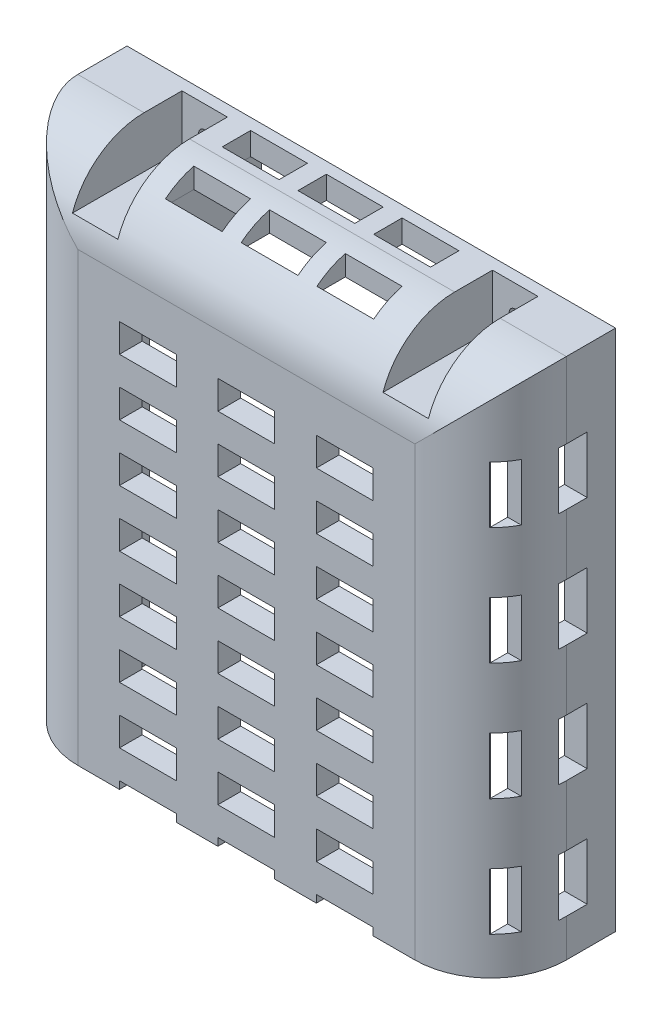
SolidWorks part; units mm, degrees
ref_plane "Plano frontal" through (0, 0, 0) normal (0, 0, 1) x (1, 0, 0)
ref_plane "Plano superior" through (0, 0, 0) normal (0, 1, 0) x (1, 0, 0)
ref_plane "Plano direito" through (0, 0, 0) normal (1, 0, 0) x (0, 0, -1)
sketch "Esboço1" plane through (0, 0, 0) normal (0, 0, 1) x (1, 0, 0)
  line L0 (-47.125, -132) -> (-47.125, -122)
  line L1 (-64.5, 138) -> (64.5, 138)
  line L2 (-64.5, 138) -> (-64.5, -138)
  line L3 (-64.5, -138) -> (64.5, -138)
  line L4 (64.5, 138) -> (64.5, -138)
  line L5 (0, -138) -> (0, 138) construction
  line L6 (-64.5, 0) -> (64.5, 0) construction
  line L7 (-58.5, 132) -> (58.5, 132) construction
  line L8 (-58.5, 132) -> (-58.5, -132) construction
  line L9 (-58.5, -132) -> (58.5, -132) construction
  line L10 (58.5, 132) -> (58.5, -132) construction
  line L11 (0, -132) -> (0, 132) construction
  line L12 (-58.5, 0) -> (58.5, 0) construction
  line L13 (-47.125, -122) -> (-58.5, -122)
  line L14 (-47, 132) -> (-47, 124.5)
  line L15 (-47, 124.5) -> (-35, 124.5)
  line L16 (-35, 124.5) -> (-35, 132)
  line L17 (-41, 130.5) -> (-41, 124.5) construction
  line L18 (-41, 130.5) -> (-35, 130.5) construction
  line L19 (-47, 132) -> (-58.5, 132)
  line L20 (-58.5, 132) -> (-58.5, -122)
  line L21 (41, 130.5) -> (35, 130.5) construction
  line L22 (41, 130.5) -> (41, 124.5) construction
  line L23 (47, 132) -> (58.5, 132)
  line L24 (35, 124.5) -> (35, 132)
  line L25 (47, 124.5) -> (35, 124.5)
  line L26 (47, 132) -> (47, 124.5)
  line L27 (58.5, 132) -> (58.5, -132) construction
  line L28 (58.5, 132) -> (58.5, -122)
  line L29 (47.125, -122) -> (58.5, -122)
  line L30 (47.125, -132) -> (47.125, -122)
  line L31 (-35, 132) -> (35, 132)
  line L32 (47.125, -132) -> (-47.125, -132)
  circle A0 centre (-53.125, -128) radius 1.6
  circle A1 centre (-41, 130.5) radius 1.6
  circle A2 centre (41, 130.5) radius 1.6
  circle A3 centre (53.125, -128) radius 1.6
  point P56 (0, 0)
  point P83 (0, 0)
  dimension "D5" = 3.2
  dimension "D8" = 3.2
  dimension "D1" = 129
  dimension "D2" = 276
  dimension "D3" = 6
  dimension "D4" = 6
  dimension "D6" = 11.375
  dimension "D7" = 10
  dimension "D9" = 23.5
  dimension "D10" = 7.5
  dimension "D11" = 6
  dimension "D12" = 6
  dimension "D13" = 6
extrude "Ressalto-extrusão1" add sketch "Esboço1" along normal blind 3
sketch "Esboço4" plane through (0, 0, 3) normal (0, 0, 1) x (1, 0, 0)
  line L0 (-64.5, 138) -> (-64.5, 72)
  line L1 (-64.5, 138) -> (-64.5, -138) construction
  line L2 (-64.5, 72) -> (-58.5, 72)
  line L3 (-58.5, 132) -> (-58.5, -122) construction
  line L4 (-58.5, 72) -> (-58.5, 132)
  line L5 (-58.5, 132) -> (-47, 132)
  line L6 (-47, 132) -> (-47, 138)
  line L7 (64.5, 138) -> (-64.5, 138) construction
  line L8 (-47, 138) -> (-64.5, 138)
  line L9 (-35, 132) -> (-35, 138)
  line L10 (-35, 138) -> (35, 138)
  line L11 (35, 138) -> (35, 132)
  line L12 (35, 132) -> (-35, 132)
  line L13 (47, 132) -> (47, 138)
  line L14 (47, 138) -> (64.5, 138)
  line L15 (64.5, 138) -> (64.5, 72)
  line L16 (64.5, -138) -> (64.5, 138) construction
  line L17 (64.5, 72) -> (58.5, 72)
  line L18 (58.5, -122) -> (58.5, 132) construction
  line L19 (58.5, 72) -> (58.5, 132)
  line L20 (58.5, 132) -> (47, 132)
  line L21 (-47.125, -132) -> (-47.125, -138)
  line L22 (-64.5, -138) -> (64.5, -138) construction
  line L23 (-47.125, -138) -> (47, -138)
  line L24 (47, -138) -> (47.125, -132)
  line L25 (47.125, -132) -> (-47.125, -132)
  line L26 (-58.5, -122) -> (-64.5, -122)
  line L27 (-64.5, -122) -> (-64.5, -22)
  line L28 (-64.5, -22) -> (-58.5, -22)
  line L29 (-58.5, -22) -> (-58.5, -122)
  line L30 (58.5, -122) -> (64.5, -122)
  line L31 (64.5, -122) -> (64.5, -22)
  line L32 (64.5, -22) -> (58.5, -22)
  line L33 (58.5, -22) -> (58.5, -122)
  dimension "D1" = 60
  dimension "D2" = 100
extrude "Ressalto-extrusão2" add sketch "Esboço4" along normal blind 24
sketch "Esboço5" plane through (0, 0, 27) normal (0, 0, 1) x (1, 0, 0)
  line L0 (-35, 132) -> (-35, 138)
  line L1 (-35, 138) -> (35, 138)
  line L2 (35, 138) -> (35, 132)
  line L3 (47, 132) -> (47, 138)
  line L4 (47, 138) -> (64.5, 138)
  line L5 (64.5, 138) -> (64.5, 72)
  line L6 (64.5, 72) -> (58.5, 72)
  line L7 (58.5, 72) -> (-64.5, 72)
  line L8 (-64.5, 72) -> (-64.5, 138)
  line L9 (-64.5, 138) -> (-47, 138)
  line L10 (-47, 138) -> (-47, 124.5)
  line L11 (-47, 124.5) -> (-35, 124.5)
  line L12 (-35, 124.5) -> (-35, 132)
  line L13 (35, 132) -> (35, 124.5)
  line L14 (35, 124.5) -> (47, 124.5)
  line L15 (47, 124.5) -> (47, 132)
  line L16 (-47.125, -138) -> (47, -138)
  line L17 (47, -138) -> (47.125, -122)
  line L18 (47.125, -122) -> (64.5, -122)
  line L19 (64.5, -122) -> (64.5, -22)
  line L20 (64.5, -22) -> (-64.5, -22)
  line L21 (-64.5, -22) -> (-64.5, -122)
  line L22 (-64.5, -122) -> (-47.125, -122)
  line L23 (-47.125, -122) -> (-47.125, -138)
extrude "Ressalto-extrusão3" add sketch "Esboço5" along normal blind 6
sketch "Esboço7" plane through (0, 0, 27) normal (0, 0, -1) x (-1, 0, 0)
  line L0 (-47, 132) -> (-53, 132)
  line L1 (-47, 132) -> (-58.5, 132) construction
  line L2 (-53, 132) -> (-53, 118.5)
  line L3 (-53, 118.5) -> (-29, 118.5)
  line L4 (-29, 118.5) -> (-29, 132)
  line L5 (35, 132) -> (-35, 132) construction
  line L6 (-29, 132) -> (-35, 132)
  line L7 (-35, 132) -> (-35, 124.5)
  line L8 (-35, 124.5) -> (-47, 124.5)
  line L9 (-47, 132) -> (-47, 124.5) construction
  line L10 (-47, 124.5) -> (-35, 124.5) construction
  line L11 (-47, 124.5) -> (-47, 132)
  line L19 (0, 0) -> (0, 50000) construction
  line L20 (58.5, -122) -> (58.5, -22) construction
  line L27 (47.125, -132) -> (47.125, -122)
  line L28 (47.125, -122) -> (58.5, -122)
  line L29 (58.5, -122) -> (58.5, -116)
  line L30 (58.5, -116) -> (41.125, -116)
  line L31 (41.125, -116) -> (41.125, -132)
  line L32 (-47.0469, -132) -> (47.125, -132) construction
  line L33 (41.125, -132) -> (47.125, -132)
  line L34 (47, 124.5) -> (47, 132)
  line L35 (35, 124.5) -> (47, 124.5)
  line L36 (35, 132) -> (35, 124.5)
  line L37 (29, 132) -> (35, 132)
  line L38 (29, 118.5) -> (29, 132)
  line L39 (53, 118.5) -> (29, 118.5)
  line L40 (53, 132) -> (53, 118.5)
  line L41 (47, 132) -> (53, 132)
  line L42 (-41.125, -132) -> (-47.125, -132)
  line L43 (-41.125, -116) -> (-41.125, -132)
  line L44 (-58.5, -116) -> (-41.125, -116)
  line L45 (-58.5, -122) -> (-58.5, -116)
  line L46 (-47.125, -122) -> (-58.5, -122)
  line L47 (-47.125, -132) -> (-47.125, -122)
  dimension "D1" = 6
  dimension "D2" = 6
  dimension "D5" = 6
extrude "Ressalto-extrusão5" add sketch "Esboço7" along normal up to vertex (27 mm away) up to point (35, 124.5, 0)
sketch "Esboço8" plane through (0, -22, 0) normal (0, 1, 0) x (1, 0, 0)
  line L0 (-58.5, -3) -> (-64.5, -3)
  line L1 (-64.5, -3) -> (-64.5, -33)
  line L2 (-64.5, -33) -> (64.5, -33)
  line L3 (64.5, -33) -> (64.5, -3)
  line L4 (64.5, -3) -> (58.5, -3)
  line L5 (58.5, -3) -> (58.5, -27)
  line L6 (58.5, -27) -> (-58.5, -27)
  line L7 (-58.5, -27) -> (-58.5, -3)
extrude "Ressalto-extrusão6" add sketch "Esboço8" along normal up to vertex (94 mm away) up to point (-58.5, 72, 27)
fillet "Filete1" radius 20 4 edges at (0, 138, 33) (-0.0625, -138, 33) (64.5, 8, 33) (-64.5, 8, 33)
sketch "Esboço9" plane through (0, 0, 33) normal (0, 0, 1) x (1, 0, 0)
  line L2 (-18.5, -106.75) -> (-7.5, -106.75) construction
  line L7 (-33.5, -103) -> (-18.5, -103) construction
  line L8 (-33.5, -103) -> (-33.5, -110.5) construction
  line L9 (-33.5, -110.5) -> (-18.5, -110.5) construction
  line L10 (-18.5, -103) -> (-18.5, -110.5) construction
  line L11 (-26, -110.5) -> (-26, -103) construction
  line L12 (-33.5, -106.75) -> (-18.5, -106.75) construction
  line L13 (-7.5, -103) -> (7.5, -103)
  line L14 (-7.5, -103) -> (-7.5, -110.5)
  line L15 (-7.5, -110.5) -> (7.5, -110.5)
  line L16 (7.5, -103) -> (7.5, -110.5)
  line L17 (0, -110.5) -> (0, -103) construction
  line L18 (-7.5, -106.75) -> (7.5, -106.75) construction
  line L19 (18.5, -103) -> (33.5, -103)
  line L20 (18.5, -103) -> (18.5, -110.5)
  line L21 (18.5, -110.5) -> (33.5, -110.5)
  line L22 (33.5, -103) -> (33.5, -110.5)
  line L23 (26, -110.5) -> (26, -103) construction
  line L24 (18.5, -106.75) -> (33.5, -106.75) construction
  line L25 (7.5, -106.75) -> (18.5, -106.75) construction
  line L26 (-33.5, -106.75) -> (-44.5, -106.75) construction
  line L27 (-44.5, 118) -> (-44.5, -118) construction
  line L28 (33.5, -106.75) -> (44.5, -106.75) construction
  line L29 (44.5, -118) -> (44.5, 118) construction
  line L30 (-44.5, -118) -> (44.5, -118) construction
  line L31 (-33.5, -88) -> (-18.5, -88)
  line L32 (-33.5, -88) -> (-33.5, -95.5)
  line L33 (-33.5, -95.5) -> (-18.5, -95.5)
  line L34 (-18.5, -88) -> (-18.5, -95.5)
  line L35 (-7.5, -88) -> (7.5, -88)
  line L36 (-7.5, -88) -> (-7.5, -95.5)
  line L37 (-7.5, -95.5) -> (7.5, -95.5)
  line L38 (7.5, -88) -> (7.5, -95.5)
  line L39 (18.5, -88) -> (33.5, -88)
  line L40 (18.5, -88) -> (18.5, -95.5)
  line L41 (18.5, -95.5) -> (33.5, -95.5)
  line L42 (33.5, -88) -> (33.5, -95.5)
  line L43 (-18.5, -91.75) -> (-7.5, -91.75) construction
  line L44 (-26, -95.5) -> (-26, -88) construction
  line L45 (-33.5, -91.75) -> (-18.5, -91.75) construction
  line L46 (0, -95.5) -> (0, -88) construction
  line L47 (-7.5, -91.75) -> (7.5, -91.75) construction
  line L48 (26, -95.5) -> (26, -88) construction
  line L49 (18.5, -91.75) -> (33.5, -91.75) construction
  line L50 (7.5, -91.75) -> (18.5, -91.75) construction
  line L51 (-33.5, -73) -> (-18.5, -73)
  line L52 (-33.5, -73) -> (-33.5, -80.5)
  line L53 (-33.5, -80.5) -> (-18.5, -80.5)
  line L54 (-18.5, -73) -> (-18.5, -80.5)
  line L55 (-7.5, -73) -> (7.5, -73)
  line L56 (-7.5, -73) -> (-7.5, -80.5)
  line L57 (-7.5, -80.5) -> (7.5, -80.5)
  line L58 (7.5, -73) -> (7.5, -80.5)
  line L59 (18.5, -73) -> (33.5, -73)
  line L60 (18.5, -73) -> (18.5, -80.5)
  line L61 (18.5, -80.5) -> (33.5, -80.5)
  line L62 (33.5, -73) -> (33.5, -80.5)
  line L63 (-18.5, -76.75) -> (-7.5, -76.75) construction
  line L64 (-26, -80.5) -> (-26, -73) construction
  line L65 (-33.5, -76.75) -> (-18.5, -76.75) construction
  line L66 (0, -80.5) -> (0, -73) construction
  line L67 (-7.5, -76.75) -> (7.5, -76.75) construction
  line L68 (26, -80.5) -> (26, -73) construction
  line L69 (18.5, -76.75) -> (33.5, -76.75) construction
  line L70 (7.5, -76.75) -> (18.5, -76.75) construction
  line L71 (-33.5, -58) -> (-18.5, -58)
  line L72 (-33.5, -58) -> (-33.5, -65.5)
  line L73 (-33.5, -65.5) -> (-18.5, -65.5)
  line L74 (-18.5, -58) -> (-18.5, -65.5)
  line L75 (-7.5, -58) -> (7.5, -58)
  line L76 (-7.5, -58) -> (-7.5, -65.5)
  line L77 (-7.5, -65.5) -> (7.5, -65.5)
  line L78 (7.5, -58) -> (7.5, -65.5)
  line L79 (18.5, -58) -> (33.5, -58)
  line L80 (18.5, -58) -> (18.5, -65.5)
  line L81 (18.5, -65.5) -> (33.5, -65.5)
  line L82 (33.5, -58) -> (33.5, -65.5)
  line L83 (-18.5, -61.75) -> (-7.5, -61.75) construction
  line L84 (-26, -65.5) -> (-26, -58) construction
  line L85 (-33.5, -61.75) -> (-18.5, -61.75) construction
  line L86 (0, -65.5) -> (0, -58) construction
  line L87 (-7.5, -61.75) -> (7.5, -61.75) construction
  line L88 (26, -65.5) -> (26, -58) construction
  line L89 (18.5, -61.75) -> (33.5, -61.75) construction
  line L90 (7.5, -61.75) -> (18.5, -61.75) construction
  line L91 (-33.5, -43) -> (-18.5, -43)
  line L92 (-33.5, -43) -> (-33.5, -50.5)
  line L93 (-33.5, -50.5) -> (-18.5, -50.5)
  line L94 (-18.5, -43) -> (-18.5, -50.5)
  line L95 (-7.5, -43) -> (7.5, -43)
  line L96 (-7.5, -43) -> (-7.5, -50.5)
  line L97 (-7.5, -50.5) -> (7.5, -50.5)
  line L98 (7.5, -43) -> (7.5, -50.5)
  line L99 (18.5, -43) -> (33.5, -43)
  line L100 (18.5, -43) -> (18.5, -50.5)
  line L101 (18.5, -50.5) -> (33.5, -50.5)
  line L102 (33.5, -43) -> (33.5, -50.5)
  line L103 (-18.5, -46.75) -> (-7.5, -46.75) construction
  line L104 (-26, -50.5) -> (-26, -43) construction
  line L105 (-33.5, -46.75) -> (-18.5, -46.75) construction
  line L106 (0, -50.5) -> (0, -43) construction
  line L107 (-7.5, -46.75) -> (7.5, -46.75) construction
  line L108 (26, -50.5) -> (26, -43) construction
  line L109 (18.5, -46.75) -> (33.5, -46.75) construction
  line L110 (7.5, -46.75) -> (18.5, -46.75) construction
  line L111 (-33.5, -28) -> (-18.5, -28)
  line L112 (-33.5, -28) -> (-33.5, -35.5)
  line L113 (-33.5, -35.5) -> (-18.5, -35.5)
  line L114 (-18.5, -28) -> (-18.5, -35.5)
  line L115 (-7.5, -28) -> (7.5, -28)
  line L116 (-7.5, -28) -> (-7.5, -35.5)
  line L117 (-7.5, -35.5) -> (7.5, -35.5)
  line L118 (7.5, -28) -> (7.5, -35.5)
  line L119 (18.5, -28) -> (33.5, -28)
  line L120 (18.5, -28) -> (18.5, -35.5)
  line L121 (18.5, -35.5) -> (33.5, -35.5)
  line L122 (33.5, -28) -> (33.5, -35.5)
  line L123 (-18.5, -31.75) -> (-7.5, -31.75) construction
  line L124 (-26, -35.5) -> (-26, -28) construction
  line L125 (-33.5, -31.75) -> (-18.5, -31.75) construction
  line L126 (0, -35.5) -> (0, -28) construction
  line L127 (-7.5, -31.75) -> (7.5, -31.75) construction
  line L128 (26, -35.5) -> (26, -28) construction
  line L129 (18.5, -31.75) -> (33.5, -31.75) construction
  line L130 (7.5, -31.75) -> (18.5, -31.75) construction
  line L131 (-33.5, -13) -> (-18.5, -13)
  line L132 (-33.5, -13) -> (-33.5, -20.5)
  line L133 (-33.5, -20.5) -> (-18.5, -20.5)
  line L134 (-18.5, -13) -> (-18.5, -20.5)
  line L135 (-7.5, -13) -> (7.5, -13)
  line L136 (-7.5, -13) -> (-7.5, -20.5)
  line L137 (-7.5, -20.5) -> (7.5, -20.5)
  line L138 (7.5, -13) -> (7.5, -20.5)
  line L139 (18.5, -13) -> (33.5, -13)
  line L140 (18.5, -13) -> (18.5, -20.5)
  line L141 (18.5, -20.5) -> (33.5, -20.5)
  line L142 (33.5, -13) -> (33.5, -20.5)
  line L143 (-18.5, -16.75) -> (-7.5, -16.75) construction
  line L144 (-26, -20.5) -> (-26, -13) construction
  line L145 (-33.5, -16.75) -> (-18.5, -16.75) construction
  line L146 (0, -20.5) -> (0, -13) construction
  line L147 (-7.5, -16.75) -> (7.5, -16.75) construction
  line L148 (26, -20.5) -> (26, -13) construction
  line L149 (18.5, -16.75) -> (33.5, -16.75) construction
  line L150 (7.5, -16.75) -> (18.5, -16.75) construction
  line L151 (-33.5, 2) -> (-18.5, 2)
  line L152 (-33.5, 2) -> (-33.5, -5.5)
  line L153 (-33.5, -5.5) -> (-18.5, -5.5)
  line L154 (-18.5, 2) -> (-18.5, -5.5)
  line L155 (-7.5, 2) -> (7.5, 2)
  line L156 (-7.5, 2) -> (-7.5, -5.5)
  line L157 (-7.5, -5.5) -> (7.5, -5.5)
  line L158 (7.5, 2) -> (7.5, -5.5)
  line L159 (18.5, 2) -> (33.5, 2)
  line L160 (18.5, 2) -> (18.5, -5.5)
  line L161 (18.5, -5.5) -> (33.5, -5.5)
  line L162 (33.5, 2) -> (33.5, -5.5)
  line L163 (-18.5, -1.75) -> (-7.5, -1.75) construction
  line L164 (-26, -5.5) -> (-26, 2) construction
  line L165 (-33.5, -1.75) -> (-18.5, -1.75) construction
  line L166 (0, -5.5) -> (0, 2) construction
  line L167 (-7.5, -1.75) -> (7.5, -1.75) construction
  line L168 (26, -5.5) -> (26, 2) construction
  line L169 (18.5, -1.75) -> (33.5, -1.75) construction
  line L170 (7.5, -1.75) -> (18.5, -1.75) construction
  line L171 (-33.5, 17) -> (-18.5, 17)
  line L172 (-33.5, 17) -> (-33.5, 9.5)
  line L173 (-33.5, 9.5) -> (-18.5, 9.5)
  line L174 (-18.5, 17) -> (-18.5, 9.5)
  line L175 (-7.5, 17) -> (7.5, 17)
  line L176 (-7.5, 17) -> (-7.5, 9.5)
  line L177 (-7.5, 9.5) -> (7.5, 9.5)
  line L178 (7.5, 17) -> (7.5, 9.5)
  line L179 (18.5, 17) -> (33.5, 17)
  line L180 (18.5, 17) -> (18.5, 9.5)
  line L181 (18.5, 9.5) -> (33.5, 9.5)
  line L182 (33.5, 17) -> (33.5, 9.5)
  line L183 (-18.5, 13.25) -> (-7.5, 13.25) construction
  line L184 (-26, 9.5) -> (-26, 17) construction
  line L185 (-33.5, 13.25) -> (-18.5, 13.25) construction
  line L186 (0, 9.5) -> (0, 17) construction
  line L187 (-7.5, 13.25) -> (7.5, 13.25) construction
  line L188 (26, 9.5) -> (26, 17) construction
  line L189 (18.5, 13.25) -> (33.5, 13.25) construction
  line L190 (7.5, 13.25) -> (18.5, 13.25) construction
  line L191 (-33.5, 32) -> (-18.5, 32)
  line L192 (-33.5, 32) -> (-33.5, 24.5)
  line L193 (-33.5, 24.5) -> (-18.5, 24.5)
  line L194 (-18.5, 32) -> (-18.5, 24.5)
  line L195 (-7.5, 32) -> (7.5, 32)
  line L196 (-7.5, 32) -> (-7.5, 24.5)
  line L197 (-7.5, 24.5) -> (7.5, 24.5)
  line L198 (7.5, 32) -> (7.5, 24.5)
  line L199 (18.5, 32) -> (33.5, 32)
  line L200 (18.5, 32) -> (18.5, 24.5)
  line L201 (18.5, 24.5) -> (33.5, 24.5)
  line L202 (33.5, 32) -> (33.5, 24.5)
  line L203 (-18.5, 28.25) -> (-7.5, 28.25) construction
  line L204 (-26, 24.5) -> (-26, 32) construction
  line L205 (-33.5, 28.25) -> (-18.5, 28.25) construction
  line L206 (0, 24.5) -> (0, 32) construction
  line L207 (-7.5, 28.25) -> (7.5, 28.25) construction
  line L208 (26, 24.5) -> (26, 32) construction
  line L209 (18.5, 28.25) -> (33.5, 28.25) construction
  line L210 (7.5, 28.25) -> (18.5, 28.25) construction
  line L211 (-33.5, 47) -> (-18.5, 47)
  line L212 (-33.5, 47) -> (-33.5, 39.5)
  line L213 (-33.5, 39.5) -> (-18.5, 39.5)
  line L214 (-18.5, 47) -> (-18.5, 39.5)
  line L215 (-7.5, 47) -> (7.5, 47)
  line L216 (-7.5, 47) -> (-7.5, 39.5)
  line L217 (-7.5, 39.5) -> (7.5, 39.5)
  line L218 (7.5, 47) -> (7.5, 39.5)
  line L219 (18.5, 47) -> (33.5, 47)
  line L220 (18.5, 47) -> (18.5, 39.5)
  line L221 (18.5, 39.5) -> (33.5, 39.5)
  line L222 (33.5, 47) -> (33.5, 39.5)
  line L223 (-18.5, 43.25) -> (-7.5, 43.25) construction
  line L224 (-26, 39.5) -> (-26, 47) construction
  line L225 (-33.5, 43.25) -> (-18.5, 43.25) construction
  line L226 (0, 39.5) -> (0, 47) construction
  line L227 (-7.5, 43.25) -> (7.5, 43.25) construction
  line L228 (26, 39.5) -> (26, 47) construction
  line L229 (18.5, 43.25) -> (33.5, 43.25) construction
  line L230 (7.5, 43.25) -> (18.5, 43.25) construction
  line L231 (-33.5, 62) -> (-18.5, 62)
  line L232 (-33.5, 62) -> (-33.5, 54.5)
  line L233 (-33.5, 54.5) -> (-18.5, 54.5)
  line L234 (-18.5, 62) -> (-18.5, 54.5)
  line L235 (-7.5, 62) -> (7.5, 62)
  line L236 (-7.5, 62) -> (-7.5, 54.5)
  line L237 (-7.5, 54.5) -> (7.5, 54.5)
  line L238 (7.5, 62) -> (7.5, 54.5)
  line L239 (18.5, 62) -> (33.5, 62)
  line L240 (18.5, 62) -> (18.5, 54.5)
  line L241 (18.5, 54.5) -> (33.5, 54.5)
  line L242 (33.5, 62) -> (33.5, 54.5)
  line L243 (-18.5, 58.25) -> (-7.5, 58.25) construction
  line L244 (-26, 54.5) -> (-26, 62) construction
  line L245 (-33.5, 58.25) -> (-18.5, 58.25) construction
  line L246 (0, 54.5) -> (0, 62) construction
  line L247 (-7.5, 58.25) -> (7.5, 58.25) construction
  line L248 (26, 54.5) -> (26, 62) construction
  line L249 (18.5, 58.25) -> (33.5, 58.25) construction
  line L250 (7.5, 58.25) -> (18.5, 58.25) construction
  line L251 (-33.5, 77) -> (-18.5, 77)
  line L252 (-33.5, 77) -> (-33.5, 69.5)
  line L253 (-33.5, 69.5) -> (-18.5, 69.5)
  line L254 (-18.5, 77) -> (-18.5, 69.5)
  line L255 (-7.5, 77) -> (7.5, 77)
  line L256 (-7.5, 77) -> (-7.5, 69.5)
  line L257 (-7.5, 69.5) -> (7.5, 69.5)
  line L258 (7.5, 77) -> (7.5, 69.5)
  line L259 (18.5, 77) -> (33.5, 77)
  line L260 (18.5, 77) -> (18.5, 69.5)
  line L261 (18.5, 69.5) -> (33.5, 69.5)
  line L262 (33.5, 77) -> (33.5, 69.5)
  line L263 (-18.5, 73.25) -> (-7.5, 73.25) construction
  line L264 (-26, 69.5) -> (-26, 77) construction
  line L265 (-33.5, 73.25) -> (-18.5, 73.25) construction
  line L266 (0, 69.5) -> (0, 77) construction
  line L267 (-7.5, 73.25) -> (7.5, 73.25) construction
  line L268 (26, 69.5) -> (26, 77) construction
  line L269 (18.5, 73.25) -> (33.5, 73.25) construction
  line L270 (7.5, 73.25) -> (18.5, 73.25) construction
  line L271 (-33.5, 92) -> (-18.5, 92)
  line L272 (-33.5, 92) -> (-33.5, 84.5)
  line L273 (-33.5, 84.5) -> (-18.5, 84.5)
  line L274 (-18.5, 92) -> (-18.5, 84.5)
  line L275 (-7.5, 92) -> (7.5, 92)
  line L276 (-7.5, 92) -> (-7.5, 84.5)
  line L277 (-7.5, 84.5) -> (7.5, 84.5)
  line L278 (7.5, 92) -> (7.5, 84.5)
  line L279 (18.5, 92) -> (33.5, 92)
  line L280 (18.5, 92) -> (18.5, 84.5)
  line L281 (18.5, 84.5) -> (33.5, 84.5)
  line L282 (33.5, 92) -> (33.5, 84.5)
  line L283 (-18.5, 88.25) -> (-7.5, 88.25) construction
  line L284 (-26, 84.5) -> (-26, 92) construction
  line L285 (-33.5, 88.25) -> (-18.5, 88.25) construction
  line L286 (0, 84.5) -> (0, 92) construction
  line L287 (-7.5, 88.25) -> (7.5, 88.25) construction
  line L288 (26, 84.5) -> (26, 92) construction
  line L289 (18.5, 88.25) -> (33.5, 88.25) construction
  line L290 (7.5, 88.25) -> (18.5, 88.25) construction
  line L291 (-33.5, 107) -> (-18.5, 107)
  line L292 (-33.5, 107) -> (-33.5, 99.5)
  line L293 (-33.5, 99.5) -> (-18.5, 99.5)
  line L294 (-18.5, 107) -> (-18.5, 99.5)
  line L295 (-7.5, 107) -> (7.5, 107)
  line L296 (-7.5, 107) -> (-7.5, 99.5)
  line L297 (-7.5, 99.5) -> (7.5, 99.5)
  line L298 (7.5, 107) -> (7.5, 99.5)
  line L299 (18.5, 107) -> (33.5, 107)
  line L300 (18.5, 107) -> (18.5, 99.5)
  line L301 (18.5, 99.5) -> (33.5, 99.5)
  line L302 (33.5, 107) -> (33.5, 99.5)
  line L303 (-18.5, 103.25) -> (-7.5, 103.25) construction
  line L304 (-26, 99.5) -> (-26, 107) construction
  line L305 (-33.5, 103.25) -> (-18.5, 103.25) construction
  line L306 (0, 99.5) -> (0, 107) construction
  line L307 (-7.5, 103.25) -> (7.5, 103.25) construction
  line L308 (26, 99.5) -> (26, 107) construction
  line L309 (18.5, 103.25) -> (33.5, 103.25) construction
  line L310 (7.5, 103.25) -> (18.5, 103.25) construction
  circle A1 centre (-26, -106.75) radius 5
  point P38 (0, -91.75)
  point P43 (26, -91.75)
  point P48 (-26, -91.75)
  point P65 (0, -76.75)
  point P70 (26, -76.75)
  point P75 (-26, -76.75)
  point P92 (0, -61.75)
  point P97 (26, -61.75)
  point P102 (-26, -61.75)
  point P112 (0, -106.75)
  point P123 (0, -46.75)
  point P128 (26, -46.75)
  point P133 (-26, -46.75)
  point P145 (26, -106.75)
  point P155 (0, -31.75)
  point P160 (26, -31.75)
  point P165 (-26, -31.75)
  point P180 (-26, -106.75)
  point P187 (0, -16.75)
  point P192 (26, -16.75)
  point P197 (-26, -16.75)
  point P214 (0, -1.75)
  point P219 (26, -1.75)
  point P224 (-26, -1.75)
  point P241 (0, 13.25)
  point P246 (26, 13.25)
  point P251 (-26, 13.25)
  point P268 (0, 28.25)
  point P273 (26, 28.25)
  point P278 (-26, 28.25)
  point P295 (0, 43.25)
  point P300 (26, 43.25)
  point P305 (-26, 43.25)
  point P322 (0, 58.25)
  point P327 (26, 58.25)
  point P332 (-26, 58.25)
  point P349 (0, 73.25)
  point P354 (26, 73.25)
  point P359 (-26, 73.25)
  point P376 (0, 88.25)
  point P381 (26, 88.25)
  point P386 (-26, 88.25)
  point P403 (0, 103.25)
  point P408 (26, 103.25)
  point P413 (-26, 103.25)
  dimension "D1" = 15
  dimension "D5" = 10
  dimension "D2" = 7.5
  dimension "D3" = 7.5
  dimension "D4" = 15
extrude "Corte-extrusão1" cut sketch "Esboço9" against normal up to next (6 mm away)
sketch "Esboço10" plane through (0, -138, 0) normal (0, -1, 0) x (1, 0, 0)
  line L0 (47, 13) -> (-47.125, 13) construction
  line L1 (-39.625, 28) -> (-24.625, 28)
  line L2 (-39.625, 28) -> (-39.625, 20.5)
  line L3 (-39.625, 20.5) -> (-24.625, 20.5)
  line L4 (-24.625, 28) -> (-24.625, 20.5)
  line L5 (-32.125, 20.5) -> (-32.125, 28) construction
  line L6 (-39.625, 24.25) -> (-24.625, 24.25) construction
  line L7 (-47.125, 32.5959) -> (-47.125, 13) construction
  line L8 (-9.625, 28) -> (5.375, 28)
  line L9 (-9.625, 28) -> (-9.625, 20.5)
  line L10 (-9.625, 20.5) -> (5.375, 20.5)
  line L11 (5.375, 28) -> (5.375, 20.5)
  line L12 (-2.125, 20.5) -> (-2.125, 28) construction
  line L13 (-9.625, 24.25) -> (5.375, 24.25) construction
  line L14 (20.375, 28) -> (35.375, 28)
  line L15 (20.375, 28) -> (20.375, 20.5)
  line L16 (20.375, 20.5) -> (35.375, 20.5)
  line L17 (35.375, 28) -> (35.375, 20.5)
  line L18 (27.875, 20.5) -> (27.875, 28) construction
  line L19 (20.375, 24.25) -> (35.375, 24.25) construction
  line L20 (-39.625, 15.5) -> (-24.625, 15.5)
  line L21 (-39.625, 15.5) -> (-39.625, 8)
  line L22 (-39.625, 8) -> (-24.625, 8)
  line L23 (-24.625, 15.5) -> (-24.625, 8)
  line L24 (-9.625, 15.5) -> (5.375, 15.5)
  line L25 (-9.625, 15.5) -> (-9.625, 8)
  line L26 (-9.625, 8) -> (5.375, 8)
  line L27 (5.375, 15.5) -> (5.375, 8)
  line L28 (20.375, 15.5) -> (35.375, 15.5)
  line L29 (20.375, 15.5) -> (20.375, 8)
  line L30 (20.375, 8) -> (35.375, 8)
  line L31 (35.375, 15.5) -> (35.375, 8)
  line L32 (-32.125, 8) -> (-32.125, 15.5) construction
  line L33 (-39.625, 11.75) -> (-24.625, 11.75) construction
  line L34 (-2.125, 8) -> (-2.125, 15.5) construction
  line L35 (-9.625, 11.75) -> (5.375, 11.75) construction
  line L36 (27.875, 8) -> (27.875, 15.5) construction
  line L37 (20.375, 11.75) -> (35.375, 11.75) construction
  point P17 (-2.125, 24.25)
  point P26 (27.875, 24.25)
  point P39 (-2.125, 11.75)
  point P48 (27.875, 11.75)
  point P53 (-32.125, 11.75)
  point P132 (-32.125, 24.25)
  dimension "D1" = 15
  dimension "D2" = 7.5
  dimension "D3" = 7.5
  dimension "D4" = 7.5
  dimension "D5" = 3
  dimension "D6" = 2
extrude "Corte-extrusão2" cut sketch "Esboço10" against normal up to vertex (6 mm away) up to point (41.125, -132, 27)
sketch "Esboço11" plane through (0, 138, 0) normal (0, 1, 0) x (1, 0, 0)
  line L0 (44.5, -33) -> (-44.5, -33) construction
  line L1 (-28.8651, -18) -> (-13.8651, -18)
  line L2 (-28.8651, -18) -> (-28.8651, -25.5)
  line L3 (-28.8651, -25.5) -> (-13.8651, -25.5)
  line L4 (-13.8651, -18) -> (-13.8651, -25.5)
  line L5 (-21.3651, -25.5) -> (-21.3651, -18) construction
  line L6 (-28.8651, -21.75) -> (-13.8651, -21.75) construction
  line L7 (-8.8651, -18) -> (6.1349, -18)
  line L8 (-8.8651, -18) -> (-8.8651, -25.5)
  line L9 (-8.8651, -25.5) -> (6.1349, -25.5)
  line L10 (6.1349, -18) -> (6.1349, -25.5)
  line L11 (-1.3651, -25.5) -> (-1.3651, -18) construction
  line L12 (-8.8651, -21.75) -> (6.1349, -21.75) construction
  line L13 (11.1349, -18) -> (26.1349, -18)
  line L14 (11.1349, -18) -> (11.1349, -25.5)
  line L15 (11.1349, -25.5) -> (26.1349, -25.5)
  line L16 (26.1349, -18) -> (26.1349, -25.5)
  line L17 (18.6349, -25.5) -> (18.6349, -18) construction
  line L18 (11.1349, -21.75) -> (26.1349, -21.75) construction
  line L19 (-8.8651, -3) -> (6.1349, -3)
  line L20 (-8.8651, -3) -> (-8.8651, -10.5)
  line L21 (-8.8651, -10.5) -> (6.1349, -10.5)
  line L22 (6.1349, -3) -> (6.1349, -10.5)
  line L23 (-1.3651, -10.5) -> (-1.3651, -3) construction
  line L24 (-8.8651, -6.75) -> (6.1349, -6.75) construction
  line L25 (11.1349, -3) -> (26.1349, -3)
  line L26 (11.1349, -3) -> (11.1349, -10.5)
  line L27 (11.1349, -10.5) -> (26.1349, -10.5)
  line L28 (26.1349, -3) -> (26.1349, -10.5)
  line L29 (18.6349, -10.5) -> (18.6349, -3) construction
  line L30 (11.1349, -6.75) -> (26.1349, -6.75) construction
  line L31 (-28.8651, -3) -> (-13.8651, -3)
  line L32 (-28.8651, -3) -> (-28.8651, -10.5)
  line L33 (-28.8651, -10.5) -> (-13.8651, -10.5)
  line L34 (-13.8651, -3) -> (-13.8651, -10.5)
  line L35 (-21.3651, -10.5) -> (-21.3651, -3) construction
  line L36 (-28.8651, -6.75) -> (-13.8651, -6.75) construction
  point P16 (-1.3651, -21.75)
  point P28 (-21.3651, -21.75)
  point P30 (18.6349, -21.75)
  point P39 (-1.3651, -6.75)
  point P48 (18.6349, -6.75)
  point P57 (-21.3651, -6.75)
  dimension "D1" = 7.5
  dimension "D2" = 15
  dimension "D3" = 7.5
  dimension "D4" = 3
  dimension "D5" = 2
extrude "Corte-extrusão3" cut sketch "Esboço11" against normal up to vertex (6 mm away) up to point (-29, 132, 27)
sketch "Esboço12" plane through (-64.5, 0, 0) normal (-1, 0, 0) x (0, 0, 1)
  line L0 (15, 118) -> (33, 118) construction
  line L1 (7.5, 118) -> (15, 118)
  line L2 (7.5, 118) -> (7.5, 103)
  line L3 (7.5, 103) -> (15, 103)
  line L4 (15, 118) -> (15, 103)
  line L5 (11.25, 103) -> (11.25, 118) construction
  line L6 (7.5, 110.5) -> (15, 110.5) construction
  line L7 (0, 138) -> (0, -138) construction
  line L8 (22.5, 118) -> (30, 118)
  line L9 (22.5, 118) -> (22.5, 103)
  line L10 (22.5, 103) -> (30, 103)
  line L11 (30, 118) -> (30, 103)
  line L12 (26.25, 103) -> (26.25, 118) construction
  line L13 (22.5, 110.5) -> (30, 110.5) construction
  line L14 (22.5, 87) -> (30, 87)
  line L15 (22.5, 87) -> (22.5, 72)
  line L16 (22.5, 72) -> (30, 72)
  line L17 (30, 87) -> (30, 72)
  line L18 (26.25, 72) -> (26.25, 87) construction
  line L19 (22.5, 79.5) -> (30, 79.5) construction
  line L20 (22.5, 56) -> (30, 56)
  line L21 (22.5, 56) -> (22.5, 41)
  line L22 (22.5, 41) -> (30, 41)
  line L23 (30, 56) -> (30, 41)
  line L24 (26.25, 41) -> (26.25, 56) construction
  line L25 (22.5, 48.5) -> (30, 48.5) construction
  line L26 (22.5, 25) -> (30, 25)
  line L27 (22.5, 25) -> (22.5, 10)
  line L28 (22.5, 10) -> (30, 10)
  line L29 (30, 25) -> (30, 10)
  line L30 (26.25, 10) -> (26.25, 25) construction
  line L31 (22.5, 17.5) -> (30, 17.5) construction
  line L32 (22.5, -6) -> (30, -6)
  line L33 (22.5, -6) -> (22.5, -21)
  line L34 (22.5, -21) -> (30, -21)
  line L35 (30, -6) -> (30, -21)
  line L36 (26.25, -21) -> (26.25, -6) construction
  line L37 (22.5, -13.5) -> (30, -13.5) construction
  line L38 (22.5, -37) -> (30, -37)
  line L39 (22.5, -37) -> (22.5, -52)
  line L40 (22.5, -52) -> (30, -52)
  line L41 (30, -37) -> (30, -52)
  line L42 (26.25, -52) -> (26.25, -37) construction
  line L43 (22.5, -44.5) -> (30, -44.5) construction
  line L44 (22.5, -68) -> (30, -68)
  line L45 (22.5, -68) -> (22.5, -83)
  line L46 (22.5, -83) -> (30, -83)
  line L47 (30, -68) -> (30, -83)
  line L48 (26.25, -83) -> (26.25, -68) construction
  line L49 (22.5, -75.5) -> (30, -75.5) construction
  line L50 (22.5, -99) -> (30, -99)
  line L51 (22.5, -99) -> (22.5, -114)
  line L52 (22.5, -114) -> (30, -114)
  line L53 (30, -99) -> (30, -114)
  line L54 (26.25, -114) -> (26.25, -99) construction
  line L55 (22.5, -106.5) -> (30, -106.5) construction
  line L56 (7.5, 87) -> (15, 87)
  line L57 (7.5, 87) -> (7.5, 72)
  line L58 (7.5, 72) -> (15, 72)
  line L59 (15, 87) -> (15, 72)
  line L60 (11.25, 72) -> (11.25, 87) construction
  line L61 (7.5, 79.5) -> (15, 79.5) construction
  line L62 (7.5, 56) -> (15, 56)
  line L63 (7.5, 56) -> (7.5, 41)
  line L64 (7.5, 41) -> (15, 41)
  line L65 (15, 56) -> (15, 41)
  line L66 (11.25, 41) -> (11.25, 56) construction
  line L67 (7.5, 48.5) -> (15, 48.5) construction
  line L68 (7.5, 25) -> (15, 25)
  line L69 (7.5, 25) -> (7.5, 10)
  line L70 (7.5, 10) -> (15, 10)
  line L71 (15, 25) -> (15, 10)
  line L72 (11.25, 10) -> (11.25, 25) construction
  line L73 (7.5, 17.5) -> (15, 17.5) construction
  line L74 (7.5, -6) -> (15, -6)
  line L75 (7.5, -6) -> (7.5, -21)
  line L76 (7.5, -21) -> (15, -21)
  line L77 (15, -6) -> (15, -21)
  line L78 (11.25, -21) -> (11.25, -6) construction
  line L79 (7.5, -13.5) -> (15, -13.5) construction
  line L80 (7.5, -37) -> (15, -37)
  line L81 (7.5, -37) -> (7.5, -52)
  line L82 (7.5, -52) -> (15, -52)
  line L83 (15, -37) -> (15, -52)
  line L84 (11.25, -52) -> (11.25, -37) construction
  line L85 (7.5, -44.5) -> (15, -44.5) construction
  line L86 (7.5, -68) -> (15, -68)
  line L87 (7.5, -68) -> (7.5, -83)
  line L88 (7.5, -83) -> (15, -83)
  line L89 (15, -68) -> (15, -83)
  line L90 (11.25, -83) -> (11.25, -68) construction
  line L91 (7.5, -75.5) -> (15, -75.5) construction
  line L92 (7.5, -99) -> (15, -99)
  line L93 (7.5, -99) -> (7.5, -114)
  line L94 (7.5, -114) -> (15, -114)
  line L95 (15, -99) -> (15, -114)
  line L96 (11.25, -114) -> (11.25, -99) construction
  line L97 (7.5, -106.5) -> (15, -106.5) construction
  point P17 (26.25, 110.5)
  point P26 (26.25, 79.5)
  point P35 (26.25, 48.5)
  point P44 (26.25, 17.5)
  point P53 (26.25, -13.5)
  point P62 (26.25, -44.5)
  point P71 (26.25, -75.5)
  point P80 (26.25, -106.5)
  point P89 (11.25, 79.5)
  point P100 (11.25, 110.5)
  point P104 (11.25, 48.5)
  point P113 (11.25, 17.5)
  point P122 (11.25, -13.5)
  point P131 (11.25, -44.5)
  point P140 (11.25, -75.5)
  point P149 (11.25, -106.5)
  dimension "D1" = 15
  dimension "D2" = 7.5
  dimension "D3" = 7.5
  dimension "D4" = 2
  dimension "D5" = 8
extrude "Corte-extrusão4" cut sketch "Esboço12" against normal up to vertex (6 mm away) up to point (-58.5, -116, 27)
mirror "Espelhar2" about plane through (0, 0, 0) normal (1, 0, 0) of "Corte-extrusão4"
sketch "Esboço13" plane through (0, 0, 33) normal (0, 0, 1) x (1, 0, 0)
  line L0 (-64.5, -37) -> (-64.5, -21) construction
  line L1 (-64.5, 0) -> (64.5, 0)
  line L2 (-64.5, 0) -> (-64.5, -149.472)
  line L3 (-64.5, -149.472) -> (64.5, -149.472)
  line L4 (64.5, 0) -> (64.5, -149.472)
  line L5 (0, -149.472) -> (0, 0) construction
  line L6 (-64.5, -74.736) -> (64.5, -74.736) construction
  line L7 (64.5, -6) -> (64.5, -21) construction
  point P380 (0, -74.736)
extrude "Corte-extrusão5" cut sketch "Esboço13" against normal up to vertex (33 mm away) up to point (-58.5, -116, 0)
